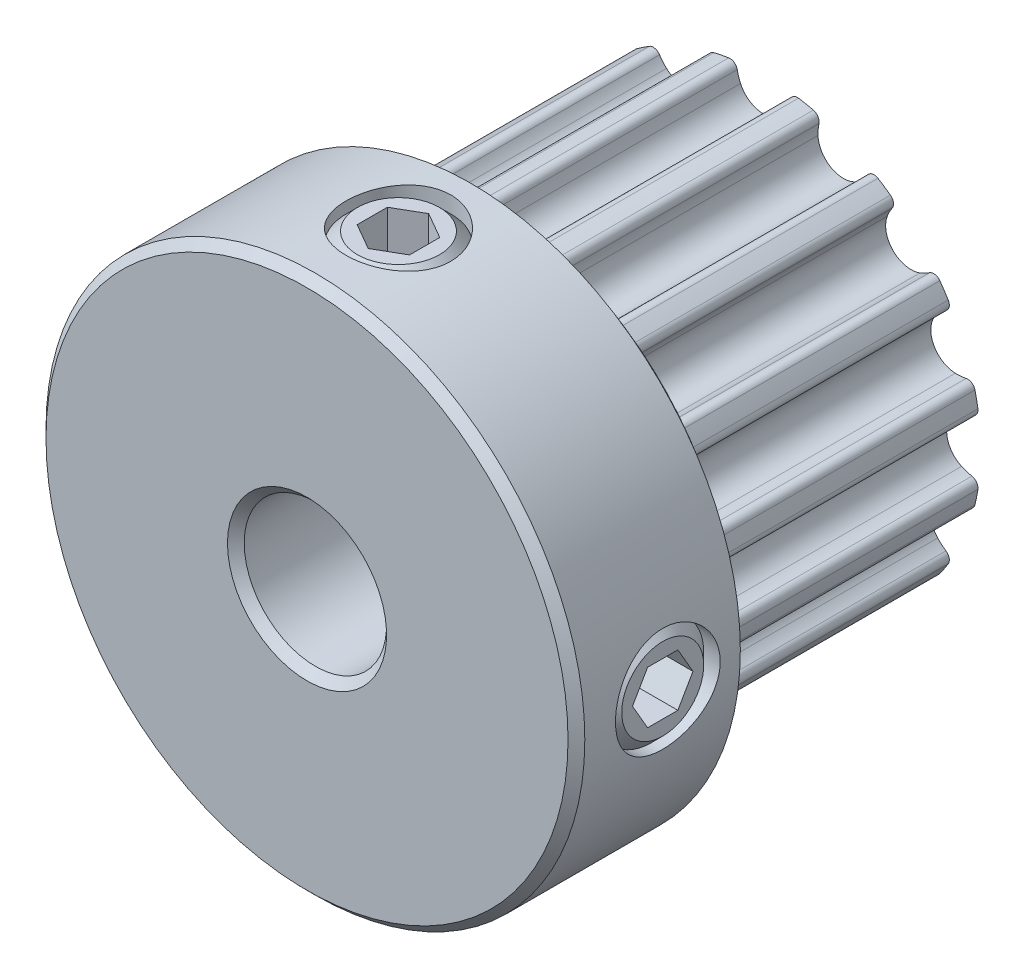
SolidWorks part; units mm, degrees
ref_plane "Front Plane" through (0, 0, 0) normal (0, 0, 1) x (1, 0, 0)
ref_plane "Top Plane" through (0, 0, 0) normal (0, 1, 0) x (1, 0, 0)
ref_plane "Right Plane" through (0, 0, 0) normal (1, 0, 0) x (0, 0, -1)
sketch "Sketch1" plane through (0, 0, 0) normal (0, 0, 1) x (1, 0, 0)
  line L1 (-2.553, 6.1245) -> (2.553, 6.1245) construction
  line L4 (0, 0) -> (0, 6.1245) construction
  line L5 (0, 6.1245) -> (0, 12.0665) construction
  line L6 (0, 7.6455) -> (2.9417, 7.0569) construction
  line L7 (2.9417, 7.0569) -> (3.8741, 6.6682) construction
  line L8 (2.9417, 7.0569) -> (2.553, 6.1245) construction
  line L9 (-2.9417, 7.0569) -> (-2.553, 6.1245) construction
  line L10 (-2.7951, 6.7052) -> (-3.7579, 9.015)
  line L11 (-3.7579, 9.015) -> (3.7579, 9.015)
  line L12 (3.7579, 9.015) -> (2.7951, 6.7052)
  circle A0 centre (0, 0) radius 7.6455 construction
  circle A1 centre (0, 0) radius 9.015 construction
  circle A2 centre (0, 0) radius 7.2645 construction
  arc A3 (-0.7739, 6.6229) -> (0.7739, 6.6229) centre (0, 6.9745) ccw
  arc A4 (-0.7739, 6.6229) -> (-0.8836, 6.9694) centre (0.61, 7.2516) cw
  arc A5 (-2.7951, 6.7052) -> (-1.1695, 7.1697) centre (0, 0) cw
  arc A6 (-0.8836, 6.9694) -> (-1.1695, 7.1697) centre (-1.1292, 6.923) ccw
  arc A7 (2.7951, 6.7052) -> (1.1695, 7.1697) centre (0, 0) ccw
  arc A8 (0.8836, 6.9694) -> (1.1695, 7.1697) centre (1.1292, 6.923) cw
  arc A9 (0.7739, 6.6229) -> (0.8836, 6.9694) centre (-0.61, 7.2516) ccw
  point P6 (0, 20.9083)
  point P11 (0, 7.6455)
  point P13 (0, 9.015)
  point P14 (0, 7.2645)
  dimension "D1" = 8.8419
  dimension "D2" = 4.421
sketch "Sketch2" plane through (0, 0, 0) normal (1, 0, 0) x (0, 0, -1)
  line L0 (-8.775, 2.3812) -> (8.775, 2.3812)
  line L1 (-8.775, 2.3812) -> (-8.775, 9.015)
  line L2 (-3.29, 9.015) -> (-8.775, 9.015)
  line L3 (-3.925, 2.3813) -> (-3.925, 9.015) construction
  line L4 (-3.925, 9.015) -> (-2.655, 9.015) construction
  line L5 (-2.655, 9.015) -> (-2.655, 7.2645) construction
  line L6 (-2.655, 7.2645) -> (7.505, 7.2645)
  line L7 (7.505, 7.2645) -> (7.505, 9.015) construction
  line L8 (7.505, 9.015) -> (8.775, 9.015) construction
  line L9 (8.775, 9.015) -> (8.775, 2.3812)
  line L10 (-8.775, 0) -> (8.775, 0) construction
  line L11 (8.14, 9.015) -> (7.505, 8.1398)
  line L12 (-2.655, 8.1398) -> (-3.29, 9.015)
  line L14 (-2.655, 8.1398) -> (-2.655, 7.2645)
  line L15 (7.505, 7.2645) -> (7.505, 8.1398)
  line L16 (8.14, 9.015) -> (8.775, 9.015)
  arc A0 (-2.655, 8.1398) -> (-3.29, 9.015) centre (-3.5757, 8.1398) ccw construction
  arc A1 (7.505, 8.1398) -> (8.14, 9.015) centre (8.4257, 8.1398) cw construction
  point P12 (-2.655, 8.1398)
  point P14 (-3.29, 9.015)
  point P20 (7.505, 8.1398)
  point P21 (8.14, 9.015)
  point P25 (7.505, 0)
  point P26 (-2.655, 0)
  dimension "OA" = 17.55
  dimension "Bore" = 4.7625
  dimension "Outside Width" = 11.43
  dimension "Inside Width" = 10.16
revolve "Revolve1" add sketch "Sketch2" angle 360 mid plane about L10
sketch "Sketch3" plane through (0, 0, 0) normal (0, 0, 1) x (1, 0, 0)
  line L6 (3.7579, 9.015) -> (-3.7579, 9.015)
  line L7 (2.7951, 6.7052) -> (3.7579, 9.015)
  line L8 (-3.7579, 9.015) -> (-2.7951, 6.7052)
  line L9 (3.7579, 9.015) -> (-3.7579, 9.015)
  line L10 (2.7951, 6.7052) -> (3.7579, 9.015)
  line L11 (-3.7579, 9.015) -> (-2.7951, 6.7052)
  arc A8 (2.7951, 6.7052) -> (1.1695, 7.1697) centre (0, 0) ccw
  arc A9 (1.1695, 7.1697) -> (0.8836, 6.9694) centre (1.1292, 6.923) ccw
  arc A10 (0.7739, 6.6229) -> (0.8836, 6.9694) centre (-0.61, 7.2516) ccw
  arc A11 (-0.7739, 6.6229) -> (0.7739, 6.6229) centre (0, 6.9745) ccw
  arc A12 (-0.8836, 6.9694) -> (-0.7739, 6.6229) centre (0.61, 7.2516) ccw
  arc A13 (-0.8836, 6.9694) -> (-1.1695, 7.1697) centre (-1.1292, 6.923) ccw
  arc A14 (-1.1695, 7.1697) -> (-2.7951, 6.7052) centre (0, 0) ccw
  arc A15 (2.7951, 6.7052) -> (1.1695, 7.1697) centre (0, 0) ccw
  arc A16 (1.1695, 7.1697) -> (0.8836, 6.9694) centre (1.1292, 6.923) ccw
  arc A17 (0.7739, 6.6229) -> (0.8836, 6.9694) centre (-0.61, 7.2516) ccw
  arc A18 (-0.7739, 6.6229) -> (0.7739, 6.6229) centre (0, 6.9745) ccw
  arc A19 (-0.8836, 6.9694) -> (-0.7739, 6.6229) centre (0.61, 7.2516) ccw
  arc A20 (-0.8836, 6.9694) -> (-1.1695, 7.1697) centre (-1.1292, 6.923) ccw
  arc A21 (-1.1695, 7.1697) -> (-2.7951, 6.7052) centre (0, 0) ccw
  dimension "D1" = 0
extrude "Cut-Extrude1" cut sketch "Sketch3" against normal up to vertex (7.505 mm away) from vertex up to point (0, 7.2645, -7.505) starting at point (0, 7.2645, 2.655)
pattern_circular "CirPattern1" count 16 over 360 about axis through (0, 0, 8.775) along (0, 0, 1) of "Cut-Extrude1"
sketch "Sketch4" plane through (0, 0, 0) normal (1, 0, 0) x (0, -1, 0)
  line L0 (0, -2.655) -> (0, -8.775) construction
  line L1 (-2.3812, -8.775) -> (2.3812, -8.775) construction
  line L2 (8.1398, -2.655) -> (-8.1398, -2.655) construction
  circle A0 centre (0, -5.715) radius 1.7526
extrude "Cut-Extrude2" cut sketch "Sketch4" along normal through all
ref_plane "Plane1" through (0, 0, 5.715) normal (0, 0, 1) x (1, 0, 0)
sketch "Sketch5" plane through (0, 0, 5.715) normal (0, 0, 1) x (1, 0, 0)
  line L0 (0, 0) -> (0, 9.015) construction
  line L1 (2.3812, -1.3716) -> (2.3812, 0)
  line L2 (2.7622, -1.7526) -> (8.462, -1.7526)
  line L3 (2.3812, 0) -> (9.015, 0) construction
  line L4 (2.3812, 0) -> (8.843, 0)
  line L5 (8.843, 0) -> (8.843, -1.3716)
  line L6 (2.7622, -1.7526) -> (2.3812, -1.3716)
  line L7 (8.843, -1.3716) -> (8.462, -1.7526)
  circle A0 centre (0, 0) radius 9.015 construction
  circle A1 centre (0, 0) radius 2.3812 construction
  point P2 (2.3812, -1.7526)
  point P11 (8.843, -1.7526)
revolve "Revolve2" add sketch "Sketch5" angle 360 mid plane about L4
sketch "Sketch6" plane through (8.843, 5.3841, 0) normal (-1, 0, 0) x (0, -1, 0)
  line L1 (5.3841, 6.7269) -> (4.5078, 6.2209)
  line L2 (4.5078, 6.2209) -> (4.5078, 5.2091)
  line L3 (4.5078, 5.2091) -> (5.3841, 4.7031)
  line L4 (5.3841, 4.7031) -> (6.2604, 5.2091)
  line L5 (6.2604, 5.2091) -> (6.2604, 6.2209)
  line L6 (6.2604, 6.2209) -> (5.3841, 6.7269)
  circle A0 centre (5.3841, 5.715) radius 0.8763 construction
  dimension "D1" = 1.7526
extrude "Cut-Extrude3" cut sketch "Sketch6" along normal blind 1.3144
pattern_circular "CirPattern3" count 2 over 90 about axis through (0, 0, 8.775) along (0, 0, 1) of "Cut-Extrude2", "Revolve2", "Cut-Extrude3"
chamfer "Chamfer1" distance 0.2807 angle 45 2 edges at (2.3812, 0, 8.775) (9.015, 0, 8.775)
ref_axis "Center Axis 1" through (0, 0, -8.775) along (0, 0, 1)
ref_plane "Contact Plane 1" through (0, 0, 8.775) normal (0, 0, 1) x (1, 0, 0)
ref_plane "Contact Plane 2" through (0, 0, -8.775) normal (0, 0, -1) x (-1, 0, 0)
sketch "Sketch7" plane through (0, 0, 2.655) normal (0, 0, -1) x (-1, 0, 0)
  circle A0 centre (0, 0) radius 9.015 construction
  circle A1 centre (0, 0) radius 9.015
extrude "Cut-Extrude4" [suppressed] cut sketch "Sketch7" along normal through all from offset 7
sketch "Sketch8" plane through (0, 0, -8.775) normal (0, 0, -1) x (-1, 0, 0)
  circle A1 centre (0, 0) radius 9.015
  circle A2 centre (0, 0) radius 9.015
  dimension "D1" = 0
extrude "Cut-Extrude5" cut sketch "Sketch8" against normal offset from surface (2.27 mm away) 1 offset beyond the face yes
sketch "Sketch9" plane through (0, 0, -6.505) normal (0, 0, -1) x (-1, 0, 0)
  arc A98 (-1.8508, -6.777) -> (-1.6633, -7.0715) centre (-1.6061, -6.8282) ccw
  arc A99 (-1.6633, -7.0715) -> (-1.1695, -7.1697) centre (0, 0) ccw
  arc A100 (-1.1695, -7.1697) -> (-0.8836, -6.9694) centre (-1.1292, -6.923) ccw
  arc A101 (-0.7739, -6.6229) -> (-0.8836, -6.9694) centre (0.61, -7.2516) ccw
  arc A102 (0.7739, -6.6229) -> (-0.7739, -6.6229) centre (0, -6.9745) ccw
  arc A103 (0.8836, -6.9694) -> (0.7739, -6.6229) centre (-0.61, -7.2516) ccw
  arc A104 (0.8836, -6.9694) -> (1.1695, -7.1697) centre (1.1292, -6.923) ccw
  arc A105 (1.1695, -7.1697) -> (1.6633, -7.0715) centre (0, 0) ccw
  arc A106 (1.6633, -7.0715) -> (1.8508, -6.777) centre (1.6061, -6.8282) ccw
  arc A107 (1.8195, -6.4149) -> (1.8508, -6.777) centre (3.3386, -6.4662) ccw
  arc A108 (3.2495, -5.8226) -> (1.8195, -6.4149) centre (2.669, -6.4436) ccw
  arc A109 (3.4834, -6.1008) -> (3.2495, -5.8226) centre (2.2115, -6.9331) ccw
  arc A110 (3.4834, -6.1008) -> (3.8242, -6.1764) centre (3.6926, -5.9639) ccw
  arc A111 (3.8242, -6.1764) -> (4.2428, -5.8967) centre (0, 0) ccw
  arc A112 (4.2428, -5.8967) -> (4.3033, -5.5529) centre (4.0968, -5.6938) ccw
  arc A113 (4.1359, -5.2303) -> (4.3033, -5.5529) centre (5.559, -4.6963) ccw
  arc A114 (5.2303, -4.1359) -> (4.1359, -5.2303) centre (4.9317, -4.9317) ccw
  arc A115 (5.5529, -4.3033) -> (5.2303, -4.1359) centre (4.6963, -5.559) ccw
  arc A116 (5.5529, -4.3033) -> (5.8967, -4.2428) centre (5.6938, -4.0968) ccw
  arc A117 (5.8967, -4.2428) -> (6.1764, -3.8242) centre (0, 0) ccw
  arc A118 (6.1764, -3.8242) -> (6.1008, -3.4834) centre (5.9639, -3.6926) ccw
  arc A119 (5.8226, -3.2495) -> (6.1008, -3.4834) centre (6.9331, -2.2115) ccw
  arc A120 (6.4149, -1.8195) -> (5.8226, -3.2495) centre (6.4436, -2.669) ccw
  arc A121 (6.777, -1.8508) -> (6.4149, -1.8195) centre (6.4662, -3.3386) ccw
  arc A122 (6.777, -1.8508) -> (7.0715, -1.6633) centre (6.8282, -1.6061) ccw
  arc A123 (7.0715, -1.6633) -> (7.1697, -1.1695) centre (0, 0) ccw
  arc A124 (7.1697, -1.1695) -> (6.9694, -0.8836) centre (6.923, -1.1292) ccw
  arc A125 (6.6229, -0.7739) -> (6.9694, -0.8836) centre (7.2516, 0.61) ccw
  arc A126 (6.6229, 0.7739) -> (6.6229, -0.7739) centre (6.9745, 0) ccw
  arc A127 (6.9694, 0.8836) -> (6.6229, 0.7739) centre (7.2516, -0.61) ccw
  arc A128 (6.9694, 0.8836) -> (7.1697, 1.1695) centre (6.923, 1.1292) ccw
  arc A129 (7.1697, 1.1695) -> (7.0715, 1.6633) centre (0, 0) ccw
  arc A130 (7.0715, 1.6633) -> (6.777, 1.8508) centre (6.8282, 1.6061) ccw
  arc A131 (6.4149, 1.8195) -> (6.777, 1.8508) centre (6.4662, 3.3386) ccw
  arc A132 (5.8226, 3.2495) -> (6.4149, 1.8195) centre (6.4436, 2.669) ccw
  arc A133 (6.1008, 3.4834) -> (5.8226, 3.2495) centre (6.9331, 2.2115) ccw
  arc A134 (6.1008, 3.4834) -> (6.1764, 3.8242) centre (5.9639, 3.6926) ccw
  arc A135 (6.1764, 3.8242) -> (5.8967, 4.2428) centre (0, 0) ccw
  arc A136 (5.8967, 4.2428) -> (5.5529, 4.3033) centre (5.6938, 4.0968) ccw
  arc A137 (5.2303, 4.1359) -> (5.5529, 4.3033) centre (4.6963, 5.559) ccw
  arc A138 (4.1359, 5.2303) -> (5.2303, 4.1359) centre (4.9317, 4.9317) ccw
  arc A139 (4.3033, 5.5529) -> (4.1359, 5.2303) centre (5.559, 4.6963) ccw
  arc A140 (4.3033, 5.5529) -> (4.2428, 5.8967) centre (4.0968, 5.6938) ccw
  arc A141 (4.2428, 5.8967) -> (3.8242, 6.1764) centre (0, 0) ccw
  arc A142 (3.8242, 6.1764) -> (3.4834, 6.1008) centre (3.6926, 5.9639) ccw
  arc A143 (3.2495, 5.8226) -> (3.4834, 6.1008) centre (2.2115, 6.9331) ccw
  arc A144 (1.8195, 6.4149) -> (3.2495, 5.8226) centre (2.669, 6.4436) ccw
  arc A145 (1.8508, 6.777) -> (1.8195, 6.4149) centre (3.3386, 6.4662) ccw
  arc A146 (1.8508, 6.777) -> (1.6633, 7.0715) centre (1.6061, 6.8282) ccw
  arc A147 (1.6633, 7.0715) -> (1.1695, 7.1697) centre (0, 0) ccw
  arc A148 (1.1695, 7.1697) -> (0.8836, 6.9694) centre (1.1292, 6.923) ccw
  arc A149 (0.7739, 6.6229) -> (0.8836, 6.9694) centre (-0.61, 7.2516) ccw
  arc A150 (-0.7739, 6.6229) -> (0.7739, 6.6229) centre (0, 6.9745) ccw
  arc A151 (-0.8836, 6.9694) -> (-0.7739, 6.6229) centre (0.61, 7.2516) ccw
  arc A152 (-0.8836, 6.9694) -> (-1.1695, 7.1697) centre (-1.1292, 6.923) ccw
  arc A153 (-1.1695, 7.1697) -> (-1.6633, 7.0715) centre (0, 0) ccw
  arc A154 (-1.6633, 7.0715) -> (-1.8508, 6.777) centre (-1.6061, 6.8282) ccw
  arc A155 (-1.8195, 6.4149) -> (-1.8508, 6.777) centre (-3.3386, 6.4662) ccw
  arc A156 (-3.2495, 5.8226) -> (-1.8195, 6.4149) centre (-2.669, 6.4436) ccw
  arc A157 (-3.4834, 6.1008) -> (-3.2495, 5.8226) centre (-2.2115, 6.9331) ccw
  arc A158 (-3.4834, 6.1008) -> (-3.8242, 6.1764) centre (-3.6926, 5.9639) ccw
  arc A159 (-3.8242, 6.1764) -> (-4.2428, 5.8967) centre (0, 0) ccw
  arc A160 (-4.2428, 5.8967) -> (-4.3033, 5.5529) centre (-4.0968, 5.6938) ccw
  arc A161 (-4.1359, 5.2303) -> (-4.3033, 5.5529) centre (-5.559, 4.6963) ccw
  arc A162 (-5.2303, 4.1359) -> (-4.1359, 5.2303) centre (-4.9317, 4.9317) ccw
  arc A163 (-5.5529, 4.3033) -> (-5.2303, 4.1359) centre (-4.6963, 5.559) ccw
  arc A164 (-5.5529, 4.3033) -> (-5.8967, 4.2428) centre (-5.6938, 4.0968) ccw
  arc A165 (-5.8967, 4.2428) -> (-6.1764, 3.8242) centre (0, 0) ccw
  arc A166 (-6.1764, 3.8242) -> (-6.1008, 3.4834) centre (-5.9639, 3.6926) ccw
  arc A167 (-5.8226, 3.2495) -> (-6.1008, 3.4834) centre (-6.9331, 2.2115) ccw
  arc A168 (-6.4149, 1.8195) -> (-5.8226, 3.2495) centre (-6.4436, 2.669) ccw
  arc A169 (-6.777, 1.8508) -> (-6.4149, 1.8195) centre (-6.4662, 3.3386) ccw
  arc A170 (-6.777, 1.8508) -> (-7.0715, 1.6633) centre (-6.8282, 1.6061) ccw
  arc A171 (-7.0715, 1.6633) -> (-7.1697, 1.1695) centre (0, 0) ccw
  arc A172 (-7.1697, 1.1695) -> (-6.9694, 0.8836) centre (-6.923, 1.1292) ccw
  arc A173 (-6.6229, 0.7739) -> (-6.9694, 0.8836) centre (-7.2516, -0.61) ccw
  arc A174 (-6.6229, -0.7739) -> (-6.6229, 0.7739) centre (-6.9745, 0) ccw
  arc A175 (-6.9694, -0.8836) -> (-6.6229, -0.7739) centre (-7.2516, 0.61) ccw
  arc A176 (-6.9694, -0.8836) -> (-7.1697, -1.1695) centre (-6.923, -1.1292) ccw
  arc A177 (-7.1697, -1.1695) -> (-7.0715, -1.6633) centre (0, 0) ccw
  arc A178 (-7.0715, -1.6633) -> (-6.777, -1.8508) centre (-6.8282, -1.6061) ccw
  arc A179 (-6.4149, -1.8195) -> (-6.777, -1.8508) centre (-6.4662, -3.3386) ccw
  arc A180 (-5.8226, -3.2495) -> (-6.4149, -1.8195) centre (-6.4436, -2.669) ccw
  arc A181 (-6.1008, -3.4834) -> (-5.8226, -3.2495) centre (-6.9331, -2.2115) ccw
  arc A182 (-6.1008, -3.4834) -> (-6.1764, -3.8242) centre (-5.9639, -3.6926) ccw
  arc A183 (-6.1764, -3.8242) -> (-5.8967, -4.2428) centre (0, 0) ccw
  arc A184 (-5.8967, -4.2428) -> (-5.5529, -4.3033) centre (-5.6938, -4.0968) ccw
  arc A185 (-5.2303, -4.1359) -> (-5.5529, -4.3033) centre (-4.6963, -5.559) ccw
  arc A186 (-4.1359, -5.2303) -> (-5.2303, -4.1359) centre (-4.9317, -4.9317) ccw
  arc A187 (-4.3033, -5.5529) -> (-4.1359, -5.2303) centre (-5.559, -4.6963) ccw
  arc A188 (-4.3033, -5.5529) -> (-4.2428, -5.8967) centre (-4.0968, -5.6938) ccw
  arc A189 (-4.2428, -5.8967) -> (-3.8242, -6.1764) centre (0, 0) ccw
  arc A190 (-3.8242, -6.1764) -> (-3.4834, -6.1008) centre (-3.6926, -5.9639) ccw
  arc A191 (-3.2495, -5.8226) -> (-3.4834, -6.1008) centre (-2.2115, -6.9331) ccw
  arc A192 (-1.8195, -6.4149) -> (-3.2495, -5.8226) centre (-2.669, -6.4436) ccw
  arc A193 (-1.8508, -6.777) -> (-1.8195, -6.4149) centre (-3.3386, -6.4662) ccw
  arc A194 (-1.8508, -6.777) -> (-1.6633, -7.0715) centre (-1.6061, -6.8282) ccw
  arc A195 (-1.6633, -7.0715) -> (-1.1695, -7.1697) centre (0, 0) ccw
  arc A196 (-1.1695, -7.1697) -> (-0.8836, -6.9694) centre (-1.1292, -6.923) ccw
  arc A197 (-0.7739, -6.6229) -> (-0.8836, -6.9694) centre (0.61, -7.2516) ccw
  arc A198 (0.7739, -6.6229) -> (-0.7739, -6.6229) centre (0, -6.9745) ccw
  arc A199 (0.8836, -6.9694) -> (0.7739, -6.6229) centre (-0.61, -7.2516) ccw
  arc A200 (0.8836, -6.9694) -> (1.1695, -7.1697) centre (1.1292, -6.923) ccw
  arc A201 (1.1695, -7.1697) -> (1.6633, -7.0715) centre (0, 0) ccw
  arc A202 (1.6633, -7.0715) -> (1.8508, -6.777) centre (1.6061, -6.8282) ccw
  arc A203 (1.8195, -6.4149) -> (1.8508, -6.777) centre (3.3386, -6.4662) ccw
  arc A204 (3.2495, -5.8226) -> (1.8195, -6.4149) centre (2.669, -6.4436) ccw
  arc A205 (3.4834, -6.1008) -> (3.2495, -5.8226) centre (2.2115, -6.9331) ccw
  arc A206 (3.4834, -6.1008) -> (3.8242, -6.1764) centre (3.6926, -5.9639) ccw
  arc A207 (3.8242, -6.1764) -> (4.2428, -5.8967) centre (0, 0) ccw
  arc A208 (4.2428, -5.8967) -> (4.3033, -5.5529) centre (4.0968, -5.6938) ccw
  arc A209 (4.1359, -5.2303) -> (4.3033, -5.5529) centre (5.559, -4.6963) ccw
  arc A210 (5.2303, -4.1359) -> (4.1359, -5.2303) centre (4.9317, -4.9317) ccw
  arc A211 (5.5529, -4.3033) -> (5.2303, -4.1359) centre (4.6963, -5.559) ccw
  arc A212 (5.5529, -4.3033) -> (5.8967, -4.2428) centre (5.6938, -4.0968) ccw
  arc A213 (5.8967, -4.2428) -> (6.1764, -3.8242) centre (0, 0) ccw
  arc A214 (6.1764, -3.8242) -> (6.1008, -3.4834) centre (5.9639, -3.6926) ccw
  arc A215 (5.8226, -3.2495) -> (6.1008, -3.4834) centre (6.9331, -2.2115) ccw
  arc A216 (6.4149, -1.8195) -> (5.8226, -3.2495) centre (6.4436, -2.669) ccw
  arc A217 (6.777, -1.8508) -> (6.4149, -1.8195) centre (6.4662, -3.3386) ccw
  arc A218 (6.777, -1.8508) -> (7.0715, -1.6633) centre (6.8282, -1.6061) ccw
  arc A219 (7.0715, -1.6633) -> (7.1697, -1.1695) centre (0, 0) ccw
  arc A220 (7.1697, -1.1695) -> (6.9694, -0.8836) centre (6.923, -1.1292) ccw
  arc A221 (6.6229, -0.7739) -> (6.9694, -0.8836) centre (7.2516, 0.61) ccw
  arc A222 (6.6229, 0.7739) -> (6.6229, -0.7739) centre (6.9745, 0) ccw
  arc A223 (6.9694, 0.8836) -> (6.6229, 0.7739) centre (7.2516, -0.61) ccw
  arc A224 (6.9694, 0.8836) -> (7.1697, 1.1695) centre (6.923, 1.1292) ccw
  arc A225 (7.1697, 1.1695) -> (7.0715, 1.6633) centre (0, 0) ccw
  arc A226 (7.0715, 1.6633) -> (6.777, 1.8508) centre (6.8282, 1.6061) ccw
  arc A227 (6.4149, 1.8195) -> (6.777, 1.8508) centre (6.4662, 3.3386) ccw
  arc A228 (5.8226, 3.2495) -> (6.4149, 1.8195) centre (6.4436, 2.669) ccw
  arc A229 (6.1008, 3.4834) -> (5.8226, 3.2495) centre (6.9331, 2.2115) ccw
  arc A230 (6.1008, 3.4834) -> (6.1764, 3.8242) centre (5.9639, 3.6926) ccw
  arc A231 (6.1764, 3.8242) -> (5.8967, 4.2428) centre (0, 0) ccw
  arc A232 (5.8967, 4.2428) -> (5.5529, 4.3033) centre (5.6938, 4.0968) ccw
  arc A233 (5.2303, 4.1359) -> (5.5529, 4.3033) centre (4.6963, 5.559) ccw
  arc A234 (4.1359, 5.2303) -> (5.2303, 4.1359) centre (4.9317, 4.9317) ccw
  arc A235 (4.3033, 5.5529) -> (4.1359, 5.2303) centre (5.559, 4.6963) ccw
  arc A236 (4.3033, 5.5529) -> (4.2428, 5.8967) centre (4.0968, 5.6938) ccw
  arc A237 (4.2428, 5.8967) -> (3.8242, 6.1764) centre (0, 0) ccw
  arc A238 (3.8242, 6.1764) -> (3.4834, 6.1008) centre (3.6926, 5.9639) ccw
  arc A239 (3.2495, 5.8226) -> (3.4834, 6.1008) centre (2.2115, 6.9331) ccw
  arc A240 (1.8195, 6.4149) -> (3.2495, 5.8226) centre (2.669, 6.4436) ccw
  arc A241 (1.8508, 6.777) -> (1.8195, 6.4149) centre (3.3386, 6.4662) ccw
  arc A242 (1.8508, 6.777) -> (1.6633, 7.0715) centre (1.6061, 6.8282) ccw
  arc A243 (1.6633, 7.0715) -> (1.1695, 7.1697) centre (0, 0) ccw
  arc A244 (1.1695, 7.1697) -> (0.8836, 6.9694) centre (1.1292, 6.923) ccw
  arc A245 (0.7739, 6.6229) -> (0.8836, 6.9694) centre (-0.61, 7.2516) ccw
  arc A246 (-0.7739, 6.6229) -> (0.7739, 6.6229) centre (0, 6.9745) ccw
  arc A247 (-0.8836, 6.9694) -> (-0.7739, 6.6229) centre (0.61, 7.2516) ccw
  arc A248 (-0.8836, 6.9694) -> (-1.1695, 7.1697) centre (-1.1292, 6.923) ccw
  arc A249 (-1.1695, 7.1697) -> (-1.6633, 7.0715) centre (0, 0) ccw
  arc A250 (-1.6633, 7.0715) -> (-1.8508, 6.777) centre (-1.6061, 6.8282) ccw
  arc A251 (-1.8195, 6.4149) -> (-1.8508, 6.777) centre (-3.3386, 6.4662) ccw
  arc A252 (-3.2495, 5.8226) -> (-1.8195, 6.4149) centre (-2.669, 6.4436) ccw
  arc A253 (-3.4834, 6.1008) -> (-3.2495, 5.8226) centre (-2.2115, 6.9331) ccw
  arc A254 (-3.4834, 6.1008) -> (-3.8242, 6.1764) centre (-3.6926, 5.9639) ccw
  arc A255 (-3.8242, 6.1764) -> (-4.2428, 5.8967) centre (0, 0) ccw
  arc A256 (-4.2428, 5.8967) -> (-4.3033, 5.5529) centre (-4.0968, 5.6938) ccw
  arc A257 (-4.1359, 5.2303) -> (-4.3033, 5.5529) centre (-5.559, 4.6963) ccw
  arc A258 (-5.2303, 4.1359) -> (-4.1359, 5.2303) centre (-4.9317, 4.9317) ccw
  arc A259 (-5.5529, 4.3033) -> (-5.2303, 4.1359) centre (-4.6963, 5.559) ccw
  arc A260 (-5.5529, 4.3033) -> (-5.8967, 4.2428) centre (-5.6938, 4.0968) ccw
  arc A261 (-5.8967, 4.2428) -> (-6.1764, 3.8242) centre (0, 0) ccw
  arc A262 (-6.1764, 3.8242) -> (-6.1008, 3.4834) centre (-5.9639, 3.6926) ccw
  arc A263 (-5.8226, 3.2495) -> (-6.1008, 3.4834) centre (-6.9331, 2.2115) ccw
  arc A264 (-6.4149, 1.8195) -> (-5.8226, 3.2495) centre (-6.4436, 2.669) ccw
  arc A265 (-6.777, 1.8508) -> (-6.4149, 1.8195) centre (-6.4662, 3.3386) ccw
  arc A266 (-6.777, 1.8508) -> (-7.0715, 1.6633) centre (-6.8282, 1.6061) ccw
  arc A267 (-7.0715, 1.6633) -> (-7.1697, 1.1695) centre (0, 0) ccw
  arc A268 (-7.1697, 1.1695) -> (-6.9694, 0.8836) centre (-6.923, 1.1292) ccw
  arc A269 (-6.6229, 0.7739) -> (-6.9694, 0.8836) centre (-7.2516, -0.61) ccw
  arc A270 (-6.6229, -0.7739) -> (-6.6229, 0.7739) centre (-6.9745, 0) ccw
  arc A271 (-6.9694, -0.8836) -> (-6.6229, -0.7739) centre (-7.2516, 0.61) ccw
  arc A272 (-6.9694, -0.8836) -> (-7.1697, -1.1695) centre (-6.923, -1.1292) ccw
  arc A273 (-7.1697, -1.1695) -> (-7.0715, -1.6633) centre (0, 0) ccw
  arc A274 (-7.0715, -1.6633) -> (-6.777, -1.8508) centre (-6.8282, -1.6061) ccw
  arc A275 (-6.4149, -1.8195) -> (-6.777, -1.8508) centre (-6.4662, -3.3386) ccw
  arc A276 (-5.8226, -3.2495) -> (-6.4149, -1.8195) centre (-6.4436, -2.669) ccw
  arc A277 (-6.1008, -3.4834) -> (-5.8226, -3.2495) centre (-6.9331, -2.2115) ccw
  arc A278 (-6.1008, -3.4834) -> (-6.1764, -3.8242) centre (-5.9639, -3.6926) ccw
  arc A279 (-6.1764, -3.8242) -> (-5.8967, -4.2428) centre (0, 0) ccw
  arc A280 (-5.8967, -4.2428) -> (-5.5529, -4.3033) centre (-5.6938, -4.0968) ccw
  arc A281 (-5.2303, -4.1359) -> (-5.5529, -4.3033) centre (-4.6963, -5.559) ccw
  arc A282 (-4.1359, -5.2303) -> (-5.2303, -4.1359) centre (-4.9317, -4.9317) ccw
  arc A283 (-4.3033, -5.5529) -> (-4.1359, -5.2303) centre (-5.559, -4.6963) ccw
  arc A284 (-4.3033, -5.5529) -> (-4.2428, -5.8967) centre (-4.0968, -5.6938) ccw
  arc A285 (-4.2428, -5.8967) -> (-3.8242, -6.1764) centre (0, 0) ccw
  arc A286 (-3.8242, -6.1764) -> (-3.4834, -6.1008) centre (-3.6926, -5.9639) ccw
  arc A287 (-3.2495, -5.8226) -> (-3.4834, -6.1008) centre (-2.2115, -6.9331) ccw
  arc A288 (-1.8195, -6.4149) -> (-3.2495, -5.8226) centre (-2.669, -6.4436) ccw
  arc A289 (-1.8508, -6.777) -> (-1.8195, -6.4149) centre (-3.3386, -6.4662) ccw
  dimension "D1" = 0
equation "\"D2@Sketch1\"= \"D1@Sketch1\" / 2"
equation "\"D1@Sketch6\" = \"Set Screw@Sketch4\" / 2"
equation "\"D1@Cut-Extrude3\" = \"D1@Sketch6\"*.75"
